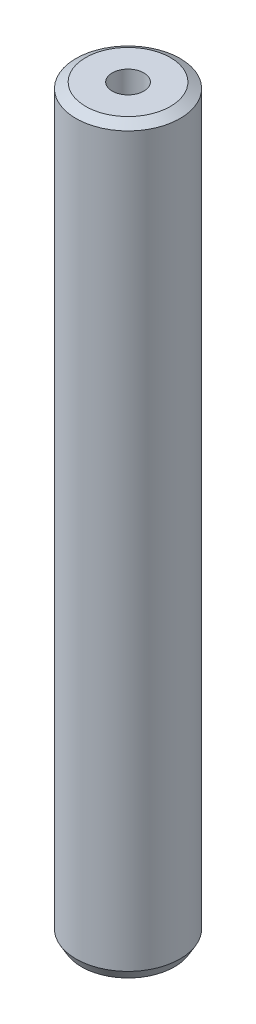
SolidWorks part; units mm, degrees
ref_plane "Front Plane" through (0, 0, 0) normal (0, 0, 1) x (1, 0, 0)
ref_plane "Top Plane" through (0, 0, 0) normal (0, 1, 0) x (1, 0, 0)
ref_plane "Right Plane" through (0, 0, 0) normal (1, 0, 0) x (0, 0, -1)
sketch "Sketch1" plane through (0, 0, 0) normal (0, 1, 0) x (1, 0, 0)
  circle A0 centre (0, 0) radius 15
  dimension "SHAFT_OD" = 30
extrude "Boss-Extrude1" add sketch "Sketch1" along normal blind 214.1383
sketch "Sketch2" plane through (0, 0, 0) normal (0, 1, 0) x (1, 0, 0)
  circle A0 centre (0, 0) radius 4.5604
  dimension "BORE_D" = 9.1207
extrude "Cut-Extrude1" cut sketch "Sketch2" along normal through all
chamfer "Chamfer1" distance 1.6139 angle 60 2 edges at (0, 214.1383, 15) (0, 0, 15) first distance on face at (0, 214.1383, 15) first distance on face at (0, 0, 4.5604)
